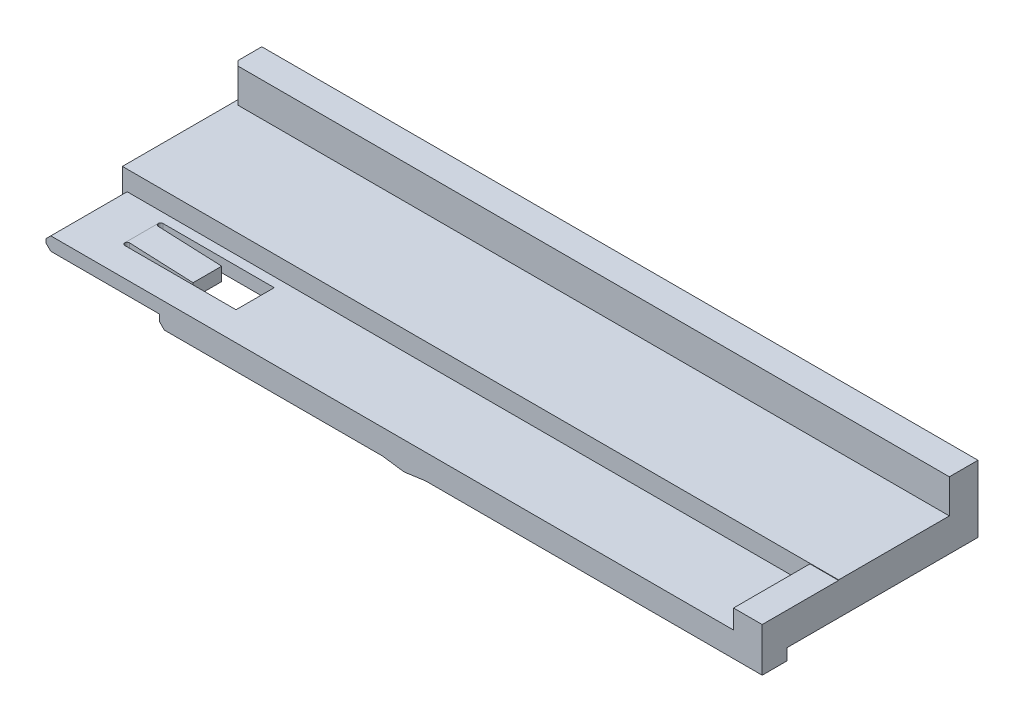
SolidWorks part; units mm, degrees
ref_plane "Plan de face" through (0, 0, 0) normal (0, 0, 1) x (1, 0, 0)
ref_plane "Plan de dessus" through (0, 0, 0) normal (0, 1, 0) x (1, 0, 0)
ref_plane "Plan de droite" through (0, 0, 0) normal (1, 0, 0) x (0, 0, -1)
sketch "Esquisse1" plane through (0, 0, 0) normal (1, 0, 0) x (0, 0, -1)
  line L0 (0, 0) -> (0, 2.6)
  line L1 (0, 2.6) -> (8, 2.6)
  line L2 (19.6, 4.65) -> (19.6, 8.2)
  line L3 (19.6, 8.2) -> (22.6, 8.2)
  line L4 (22.6, 8.2) -> (22.6, 1.2)
  line L5 (22.6, 1.2) -> (2.6, 1.2)
  line L6 (2.6, 1.2) -> (2.6, 0)
  line L7 (2.6, 0) -> (0, 0)
  line L8 (8, 2.6) -> (8, 4.65)
  line L9 (8, 4.65) -> (19.6, 4.65)
  dimension "D1" = 2.6
  dimension "D2" = 2.6
  dimension "D3" = 1.4
  dimension "D4" = 3
  dimension "D5" = 8
  dimension "D6" = 2.05
  dimension "D7" = 11.6
  dimension "D8" = 7
extrude "Boss.-Extru.1" add sketch "Esquisse1" along normal blind 75
sketch "Esquisse2" plane through (0, 2.6, 0) normal (0, 1, 0) x (1, 0, 0)
  line L1 (5, 7) -> (16.9, 7)
  line L2 (5, 7) -> (5, 3)
  line L3 (5, 3) -> (16.9, 3)
  line L4 (16.9, 7) -> (16.9, 3)
  line L5 (75, 8) -> (75, 0) construction
  line L6 (75, 8) -> (0, 8) construction
  line L7 (0, 8) -> (0, 0) construction
  dimension "D1" = 58.1
  dimension "D2" = 1
  dimension "D3" = 4
  dimension "D4" = 5
extrude "Enlèv. mat.-Extru.1" cut sketch "Esquisse2" against normal blind 10 contours L4 L3 L2 L1
sketch "Esquisse3" plane through (0, 0, -7) normal (0, 0, 1) x (1, 0, 0)
  line L0 (5, 2.6) -> (11.9, 2.3)
  line L1 (11.9, 2.3) -> (11.9, 0.9)
  line L2 (5, 2.6) -> (16.9, 2.6) construction
  line L3 (5, 2.6) -> (5, 1.2)
  line L4 (5, 1.2) -> (5, 2.6) construction
  line L5 (5, 1.2) -> (11.9, 0.9)
  line L7 (75, 2.6) -> (75, 0) construction
  line L8 (5, 1.2) -> (16.9, 1.2) construction
  dimension "D1" = 0.3
  dimension "D2" = 63.1
extrude "Boss.-Extru.2" add sketch "Esquisse3" along normal blind 3 from offset 0.5
sketch "Esquisse4" plane through (0, 2.6, 0) normal (0, 1, 0) x (1, 0, 0)
  line L0 (75, 8) -> (75, 0) construction
  line L1 (72, 8) -> (75, 8)
  line L2 (72, 8) -> (72, 0)
  line L3 (72, 0) -> (75, 0)
  line L4 (75, 8) -> (75, 0)
  line L5 (75, 8) -> (0, 8) construction
  dimension "D1" = 3
extrude "Boss.-Extru.3" add sketch "Esquisse4" along normal blind 2
sketch "Esquisse5" plane through (0, 0, 0) normal (0, 0, 1) x (1, 0, 0)
  line L0 (75, 1.2) -> (0, 1.2) construction
  line L1 (0, 0) -> (11.9, 0)
  line L2 (0, 0) -> (0, 1.2)
  line L3 (0, 1.2) -> (11.9, 1.2)
  line L4 (11.9, 0) -> (11.9, 1.2)
  line L5 (11.9, 0.9) -> (11.9, 2.3) construction
extrude "Enlèv. mat.-Extru.2" cut sketch "Esquisse5" against normal blind 3
chamfer "Chanfrein1" distance 0.5 angle 45 4 edges at (0, 2.6, -4) (0, 1.2, -11.3) (11.9, 0, -1.3) (0, 6.425, -19.6)
fillet "Congé1" radius 0.25 4 edges at (5, 1.9, -7) (5, 1.9, -6.5) (5, 1.9, -3) (5, 1.9, -3.5)
ref_plane "Plan1" through (37.5, 0, 0) normal (1, 0, 0) x (0, 0, -1)
sketch "Esquisse6" plane through (37.5, 0, 0) normal (1, 0, 0) x (0, 0, -1)
  line L0 (0, 0) -> (0, -0.3)
  line L1 (0, -0.3) -> (2.9, -0.3)
  line L2 (2.9, -0.3) -> (2.9, 1.2)
  line L3 (2.6, 1.2) -> (22.6, 1.2) construction
  line L4 (2.9, 1.2) -> (2.6, 1.2)
  line L5 (2.6, 1.2) -> (2.6, 0)
  line L6 (2.6, 0) -> (0, 0)
  line L7 (8, 2.6) -> (0, 2.6) construction
  dimension "D1" = 2.9
  dimension "D2" = 2.9
extrude "Boss.-Extru.4" add sketch "Esquisse6" along normal mid plane 0.2
chamfer "Chanfrein2" distance 0.3 angle 82 2 edges at (37.4, 0.6, -2.6) (37.4, 0, -1.3) first distance on face at (37.4, 0.3, -1.8333)
chamfer "Chanfrein3" distance 0.3 angle 82 2 edges at (37.6, 0.6, -2.6) (37.6, 0, -1.3) first distance on face at (37.6, 0.3, -1.8333)
